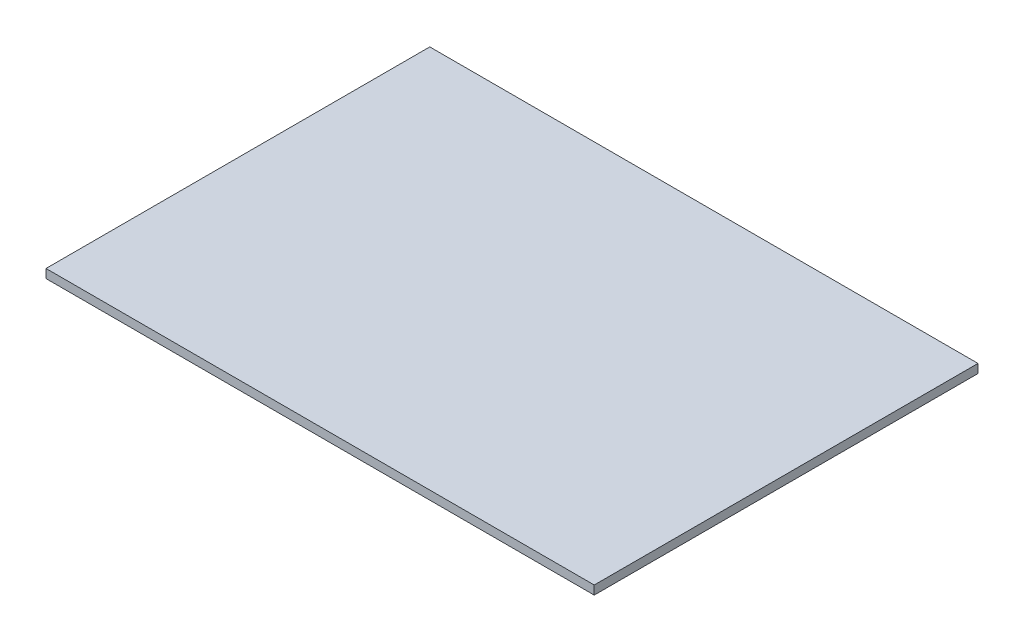
SolidWorks part; units mm, degrees
ref_plane "Front Plane" through (0, 0, 0) normal (0, 0, 1) x (1, 0, 0)
ref_plane "Top Plane" through (0, 0, 0) normal (0, 1, 0) x (1, 0, 0)
ref_plane "Right Plane" through (0, 0, 0) normal (1, 0, 0) x (0, 0, -1)
sketch "Sketch2" plane through (0, 0, 0) normal (0, 1, 0) x (1, 0, 0)
  line L1 (-50, -35) -> (50, -35)
  line L2 (-50, -35) -> (-50, 35)
  line L3 (-50, 35) -> (50, 35)
  line L4 (50, -35) -> (50, 35)
  line L5 (-50, -35) -> (50, 35) construction
  line L6 (-50, 35) -> (50, -35) construction
  point P0 (0, 0)
  dimension "D1" = 100
  dimension "D2" = 70
extrude "Boss-Extrude1" add sketch "Sketch2" along normal blind 1.6
